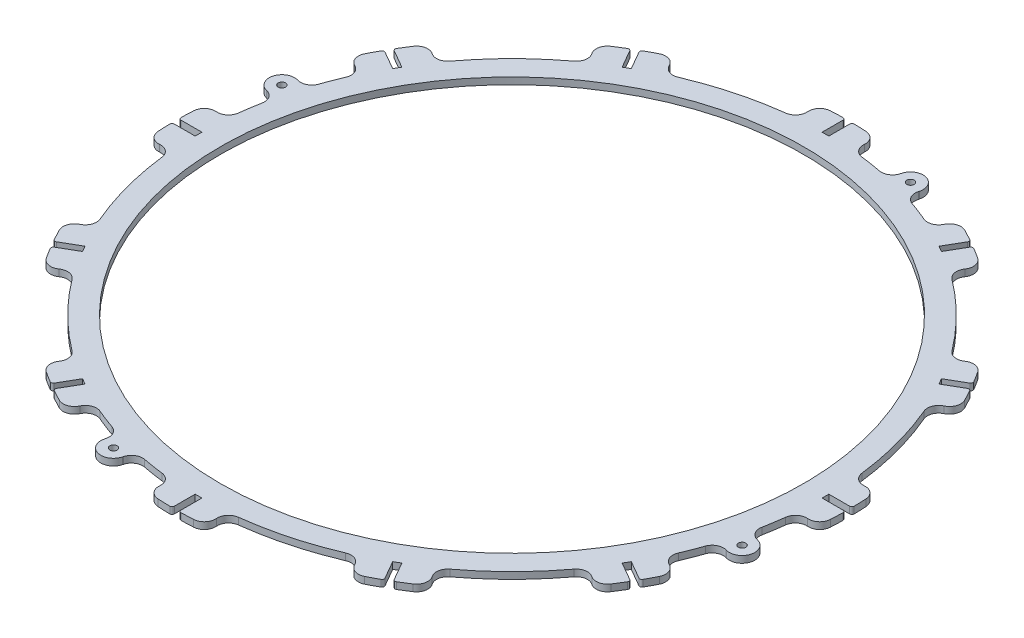
SolidWorks part; units mm, degrees
ref_plane "Front Plane" through (0, 0, 0) normal (0, 0, 1) x (1, 0, 0)
ref_plane "Top Plane" through (0, 0, 0) normal (0, 1, 0) x (1, 0, 0)
ref_plane "Right Plane" through (0, 0, 0) normal (1, 0, 0) x (0, 0, -1)
sketch "Sketch1" plane through (0, 0, 0) normal (0, 1, 0) x (1, 0, 0)
  line L1 (0, 130) -> (0, 150) construction
  circle A0 centre (0, 0) radius 150
  circle A1 centre (0, 0) radius 130
  point P7 (0, 0)
  dimension "D1" = 300
  dimension "D2" = 20
extrude "Boss-Extrude1" add sketch "Sketch1" along normal blind 3
sketch "Sketch2" plane through (0, 3, 0) normal (0, 1, 0) x (1, 0, 0)
  line L0 (0, 0) -> (0, 150) construction
  line L1 (-1.5, 139.7) -> (1.5, 139.7)
  line L2 (-1.5, 139.7) -> (-1.5, 152.3249)
  line L3 (-1.5, 152.3249) -> (1.5, 152.3249)
  line L4 (1.5, 152.3249) -> (1.5, 139.7)
  circle A0 centre (0, 0) radius 150 construction
  point P8 (0, 139.7)
  dimension "D1" = 139.7
  dimension "D2" = 3
extrude "Cut-Extrude1" cut sketch "Sketch2" against normal blind 3
fillet "Fillet1" radius 1 2 edges at (1.5, 1.5, -149.9925) (-1.5, 1.5, -149.9925)
pattern_circular "CirPattern1" count 12 over 360 about axis through (0, 3, 0) along (0, -1, 0) of "Fillet1", "Cut-Extrude1" reverse direction yes
sketch "Sketch3" plane through (0, 3, 0) normal (0, 1, 0) x (1, 0, 0)
  line L0 (0, 0) -> (13.0734, 149.4292) construction
  line L1 (0, 0) -> (0, 150) construction
  line L2 (0, 0) -> (69.85, 120.9837) construction
  line L3 (68.551, 121.7337) -> (71.149, 120.2337) construction
  line L4 (0, 0) -> (63.3927, 135.9462) construction
  line L5 (12.2018, 139.4673) -> (13.0734, 149.4292)
  line L6 (59.1666, 126.8831) -> (63.3927, 135.9462)
  arc A0 (72.8098, 131.1439) -> (2.5168, 149.9789) centre (0, 0) ccw construction
  arc A1 (12.2018, 139.4673) -> (59.1666, 126.8831) centre (0, 0) cw
  circle A2 centre (0, 0) radius 130 construction
  arc A3 (13.0734, 149.4292) -> (63.3927, 135.9462) centre (0, 0) cw
  dimension "D1" = 5
  dimension "D2" = 5
  dimension "D3" = 10
extrude "Cut-Extrude2" cut sketch "Sketch3" against normal blind 10
fillet "Fillet2" radius 5 4 edges at (63.3927, 1.5, -135.9462) (13.0734, 1.5, -149.4292) (12.2018, 1.5, -139.4673) (59.1666, 1.5, -126.8831)
pattern_circular "CirPattern2" count 12 over 360 about axis through (0, 3, 0) along (0, -1, 0) of "Cut-Extrude2", "Fillet2" reverse direction yes
sketch "Sketch5" plane through (0, 3, 0) normal (0, 1, 0) x (1, 0, 0)
  line L0 (0, 0) -> (0, 185.9307) construction
  line L1 (0, 0) -> (37.5288, 140.0592) construction
  line L2 (37.5288, 140.0592) -> (35.367, 131.9913) construction
  line L3 (42.9862, 138.5969) -> (42.8849, 138.2186)
  line L4 (32.0713, 141.5216) -> (31.9699, 141.1433)
  line L5 (41.6626, 133.6571) -> (40.8244, 130.5289)
  line L6 (30.7477, 136.5818) -> (29.9095, 133.4536)
  line L7 (138.5969, -42.9862) -> (138.2186, -42.8849)
  line L8 (141.5216, -32.0713) -> (141.1433, -31.9699)
  line L9 (133.6571, -41.6626) -> (130.5289, -40.8244)
  line L10 (136.5818, -30.7477) -> (133.4536, -29.9095)
  line L11 (0, 0) -> (140.0592, -37.5288) construction
  line L12 (140.0592, -37.5288) -> (131.9913, -35.367) construction
  line L13 (-42.9862, -138.5969) -> (-42.8849, -138.2186)
  line L14 (-32.0713, -141.5216) -> (-31.9699, -141.1433)
  line L15 (-41.6626, -133.6571) -> (-40.8244, -130.5289)
  line L16 (-30.7477, -136.5818) -> (-29.9095, -133.4536)
  line L17 (0, 0) -> (-37.5288, -140.0592) construction
  line L18 (-37.5288, -140.0592) -> (-35.367, -131.9913) construction
  line L19 (-138.5969, 42.9862) -> (-138.2186, 42.8849)
  line L20 (-141.5216, 32.0713) -> (-141.1433, 31.9699)
  line L21 (-133.6571, 41.6626) -> (-130.5289, 40.8244)
  line L22 (-136.5818, 30.7477) -> (-133.4536, 29.9095)
  line L23 (0, 0) -> (-140.0592, 37.5288) construction
  line L24 (-140.0592, 37.5288) -> (-131.9913, 35.367) construction
  circle A0 centre (37.5288, 140.0592) radius 1.65
  arc A1 (42.9862, 138.5969) -> (32.0713, 141.5216) centre (37.5288, 140.0592) ccw
  arc A2 (29.9095, 133.4536) -> (40.8244, 130.5289) centre (35.367, 131.9913) ccw
  arc A36 (54.7561, 128.8479) -> (17.0038, 138.9636) centre (0, 0) ccw construction
  arc A37 (46.0692, 132.203) -> (41.6626, 133.6571) centre (0, 0) ccw
  arc A38 (30.7477, 136.5818) -> (26.2044, 137.5257) centre (0, 0) ccw
  arc A39 (31.9699, 141.1433) -> (26.2044, 137.5257) centre (27.1403, 142.4374) cw
  arc A40 (42.8849, 138.2186) -> (46.0692, 132.203) centre (47.7145, 136.9245) ccw
  circle A41 centre (140.0592, -37.5288) radius 1.65
  arc A42 (138.5969, -42.9862) -> (141.5216, -32.0713) centre (140.0592, -37.5288) ccw
  arc A43 (133.4536, -29.9095) -> (130.5289, -40.8244) centre (131.9913, -35.367) ccw
  arc A44 (132.203, -46.0692) -> (133.6571, -41.6626) centre (0, 0) ccw
  arc A45 (136.5818, -30.7477) -> (137.5257, -26.2044) centre (0, 0) ccw
  arc A46 (141.1433, -31.9699) -> (137.5257, -26.2044) centre (142.4374, -27.1403) cw
  arc A47 (138.2186, -42.8849) -> (132.203, -46.0692) centre (136.9245, -47.7145) ccw
  circle A48 centre (-37.5288, -140.0592) radius 1.65
  arc A49 (-42.9862, -138.5969) -> (-32.0713, -141.5216) centre (-37.5288, -140.0592) ccw
  arc A50 (-29.9095, -133.4536) -> (-40.8244, -130.5289) centre (-35.367, -131.9913) ccw
  arc A51 (-46.0692, -132.203) -> (-41.6626, -133.6571) centre (0, 0) ccw
  arc A52 (-30.7477, -136.5818) -> (-26.2044, -137.5257) centre (0, 0) ccw
  arc A53 (-31.9699, -141.1433) -> (-26.2044, -137.5257) centre (-27.1403, -142.4374) cw
  arc A54 (-42.8849, -138.2186) -> (-46.0692, -132.203) centre (-47.7145, -136.9245) ccw
  circle A55 centre (-140.0592, 37.5288) radius 1.65
  arc A56 (-138.5969, 42.9862) -> (-141.5216, 32.0713) centre (-140.0592, 37.5288) ccw
  arc A57 (-133.4536, 29.9095) -> (-130.5289, 40.8244) centre (-131.9913, 35.367) ccw
  arc A58 (-132.203, 46.0692) -> (-133.6571, 41.6626) centre (0, 0) ccw
  arc A59 (-136.5818, 30.7477) -> (-137.5257, 26.2044) centre (0, 0) ccw
  arc A60 (-141.1433, 31.9699) -> (-137.5257, 26.2044) centre (-142.4374, 27.1403) cw
  arc A61 (-138.2186, 42.8849) -> (-132.203, 46.0692) centre (-136.9245, 47.7145) ccw
  point P5 (36.4479, 136.0253)
  point P27 (136.0253, -36.4479)
  point P43 (-36.4479, -136.0253)
  point P59 (-136.0253, 36.4479)
  point P102 (0, 0)
  point P202 (0, 0)
  dimension "D2" = 3.3
  dimension "D3" = 4
  dimension "D1" = 5
  dimension "D5" = 5
  dimension "D4" = 15
  dimension "D6" = 4
extrude "Boss-Extrude3" add sketch "Sketch5" against normal up to surface (3 mm away) up to face at (0, 0, 0)
equation "\"D2@Sketch3\"=\"D1@Sketch3\""
